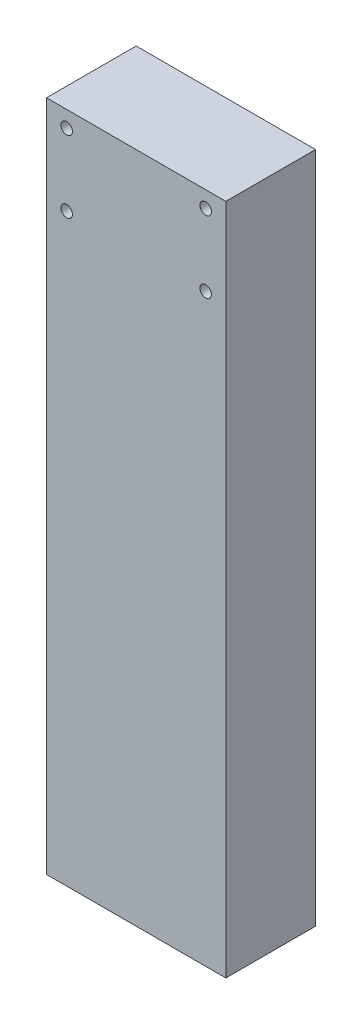
SolidWorks part; units mm, degrees
material "Oak"
ref_plane "Front Plane" through (0, 0, 0) normal (0, 0, 1) x (1, 0, 0)
ref_plane "Top Plane" through (0, 0, 0) normal (0, 1, 0) x (1, 0, 0)
ref_plane "Right Plane" through (0, 0, 0) normal (1, 0, 0) x (0, 0, -1)
sketch "Sketch1" plane through (0, 0, 0) normal (0, 1, 0) x (1, 0, 0)
  line L1 (-50.8, -25.4) -> (50.8, -25.4)
  line L2 (-50.8, -25.4) -> (-50.8, 25.4)
  line L3 (-50.8, 25.4) -> (50.8, 25.4)
  line L4 (50.8, -25.4) -> (50.8, 25.4)
  line L5 (-50.8, -25.4) -> (50.8, 25.4) construction
  line L6 (-50.8, 25.4) -> (50.8, -25.4) construction
  point P0 (0, 0)
  dimension "D1" = 101.6
  dimension "D2" = 50.8
extrude "Boss-Extrude1" add sketch "Sketch1" along normal blind 381
hole_wizard "1/4 Clearance Hole2" positions "Sketch4" profile "Sketch5" hole size "1/4" standard "ANSI Inch" end condition through all
sketch "Sketch4" plane through (0, 205.7654, 25.4) normal (0, 0, 1) x (1, 0, 0)
  point P0 (39.37, 165.9953)
  point P1 (39.37, 125.3553)
  point P2 (-39.37, 125.3553)
  point P3 (-39.37, 165.9953)
sketch "Sketch5" plane through (39.37, 371.7607, 25.4) normal (1, 0, 0) x (0, -1, 0)
  line L0 (0, 0) -> (0, 50.8)
  line L1 (0, 50.8) -> (3.2639, 50.8)
  line L2 (3.2639, 50.8) -> (3.2639, 0)
  line L3 (3.2639, 0) -> (0, 0)
  line L4 (0, -6.35) -> (0, 107.95) construction
  dimension "Thru Hole Dia." = 6.5278
  dimension "Thru Hole Depth" = 50.8
